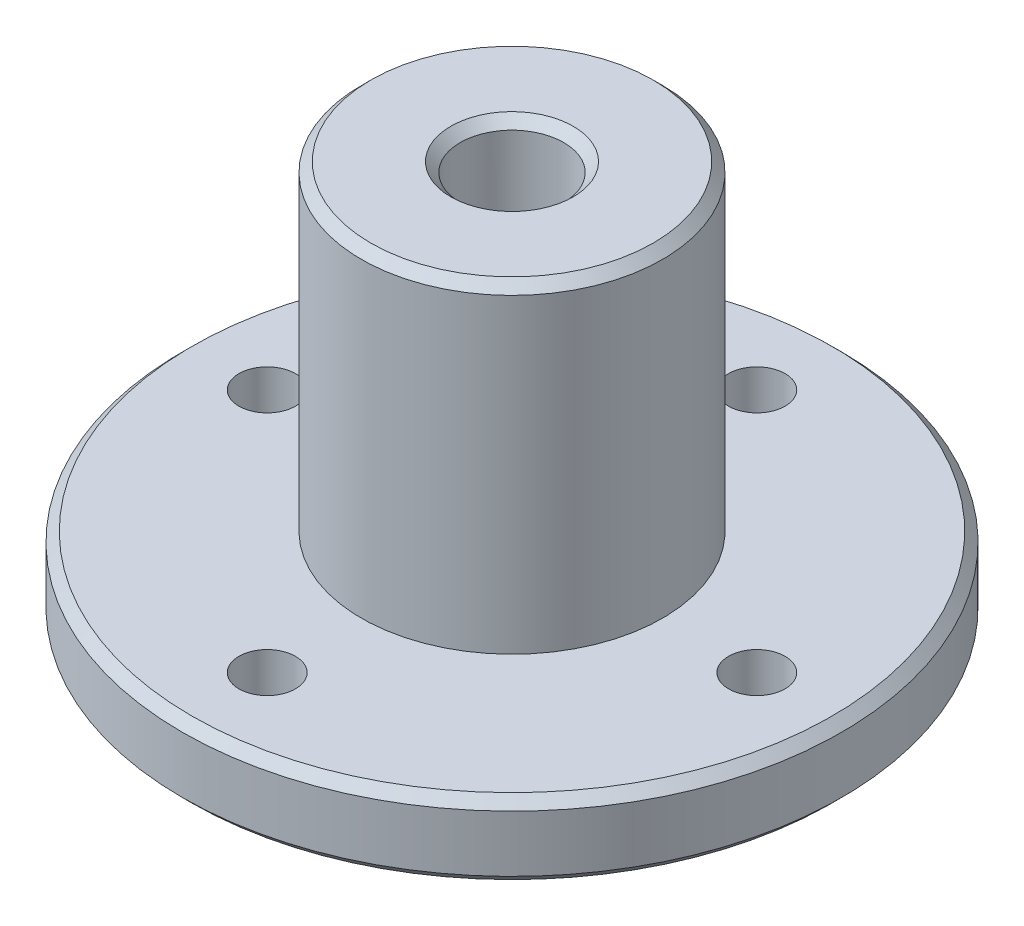
SolidWorks part; units mm, degrees
ref_plane "Front Plane" through (0, 0, 0) normal (0, 0, 1) x (1, 0, 0)
ref_plane "Top Plane" through (0, 0, 0) normal (0, 1, 0) x (1, 0, 0)
ref_plane "Right Plane" through (0, 0, 0) normal (1, 0, 0) x (0, 0, -1)
sketch "Sketch1" plane through (0, 0, 0) normal (0, 1, 0) x (1, 0, 0)
  circle A0 centre (0, 0) radius 8
  circle A1 centre (0, 0) radius 17.5
  circle A2 centre (0, 0) radius 2.75
  dimension "D1" = 35
  dimension "D2" = 16
  dimension "D3" = 5.5
extrude "Boss-Extrude1" add sketch "Sketch1" along normal blind 4 contours A1 A0 | A0 A2 | A2 region at (-7.7737, 0, 0) region at (-17.005, 0, 0) region at (0, 0, 0)
extrude "Boss-Extrude2" add sketch "Sketch1<3>" along normal blind 4 contours A0 | A2
sketch "Sketch1<3>" plane through (0, 0, 0) normal (0, 1, 0) x (1, 0, 0) same geometry as "Sketch1"
extrude "Boss-Extrude3" add sketch "Sketch1<4>" along normal blind 21 contours A0 | A2
sketch "Sketch1<4>" plane through (0, 0, 0) normal (0, 1, 0) x (1, 0, 0) same geometry as "Sketch1"
ref_plane "Plane1" through (0, 16, 0) normal (0, 1, 0) x (1, 0, 0)
sketch "Sketch2" plane through (0, 16, 0) normal (0, 1, 0) x (1, 0, 0)
  circle A0 centre (0, 0) radius 5.5
  dimension "D1" = 11
extrude "Cut-Extrude1" cut sketch "Sketch2" against normal blind 21
ref_plane "Plane2" through (0, 13.1, 0) normal (0, 1, 0) x (1, 0, 0)
sketch "Sketch4" plane through (0, 13.1, 0) normal (0, 1, 0) x (1, 0, 0)
  circle A0 centre (0, 0) radius 6
  dimension "D1" = 12
extrude "Cut-Extrude2" cut sketch "Sketch4" against normal blind 1.1
sketch "Sketch5" plane through (0, 4, 0) normal (0, 1, 0) x (1, 0, 0)
  circle A0 centre (0, 0) radius 13 construction
  circle A1 centre (0, 13) radius 1.5
  circle A2 centre (13, 0) radius 1.5
  circle A3 centre (0, -13) radius 1.5
  circle A4 centre (-13, 0) radius 1.5
  point P5 (15.3548, 0)
  point P6 (0, 0)
  point P13 (0, 0)
  dimension "D1" = 26
  dimension "D2" = 3
  dimension "D3" = 4
extrude "Cut-Extrude3" cut sketch "Sketch5" against normal blind 21.1
chamfer "Chamfer1" distance 0.5 angle 45 9 edges at (0, 0, 17.5) (0, 0, 5.5) (-13, 0, 1.5) (0, 0, 14.5) (13, 0, 1.5) (0, 0, -11.5) (0, 21, 2.75) (0, 21, 8) (0, 4, 17.5)
